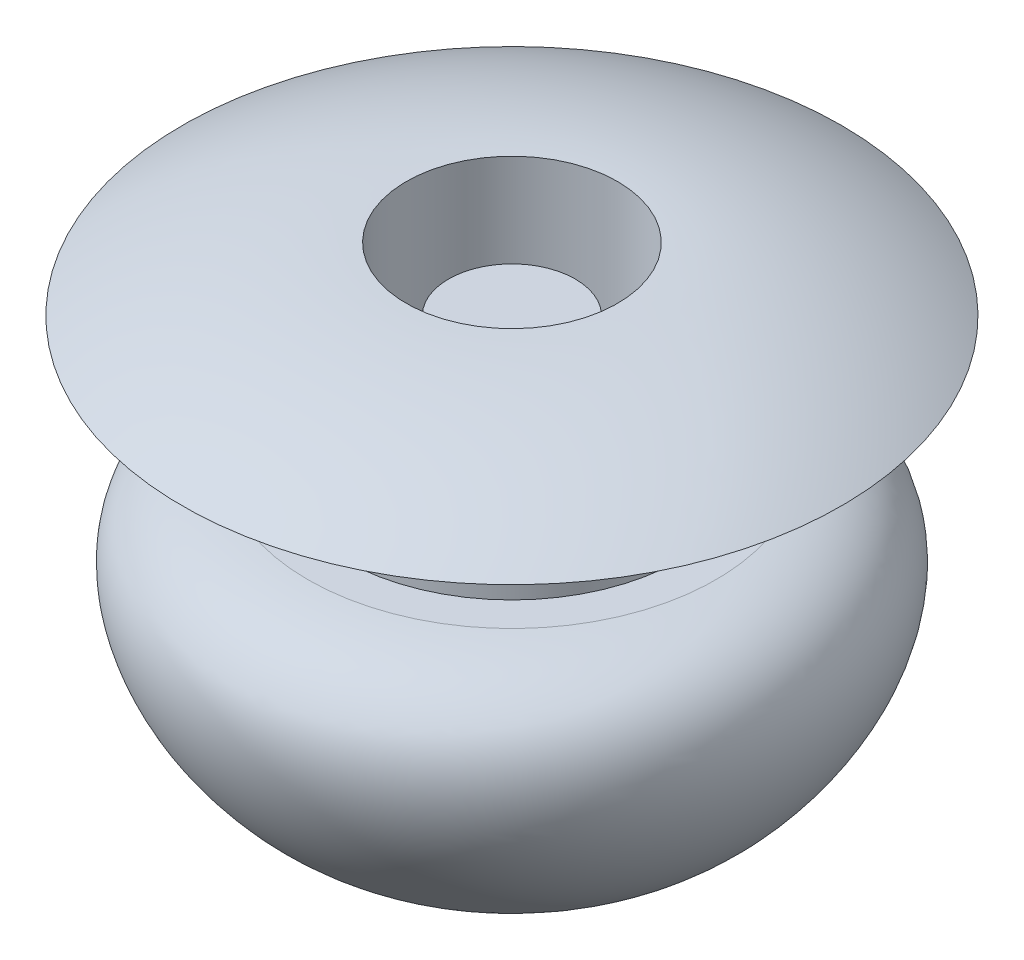
SolidWorks part; units mm, degrees
material "AISI 316 Stal nierdzewna odprężona (SS)"
ref_plane "Płaszczyzna przednia" through (0, 0, 0) normal (0, 0, 1) x (1, 0, 0)
ref_plane "Płaszczyzna górna" through (0, 0, 0) normal (0, 1, 0) x (1, 0, 0)
ref_plane "Płaszczyzna prawa" through (0, 0, 0) normal (1, 0, 0) x (0, 0, -1)
sketch "Szkic1" plane through (0, 0, 0) normal (1, 0, 0) x (0, 0, -1)
  line L1 (0, 0) -> (-0.75, 0)
  line L2 (-0.75, 0) -> (-0.75, -1.7007)
  line L3 (-0.75, -1.7007) -> (-1.25, -1.7007)
  line L4 (-1.25, -1.7007) -> (-1.25, 0.75)
  line L5 (-3.9, 0) -> (-2, 0)
  line L6 (-2, 0) -> (-2, -1.5)
  line L7 (-2, -1.5) -> (-2.4139, -1.5)
  line L8 (0, 0) -> (0, 0.4842) construction
  line L9 (0, -1.7007) -> (0, 0)
  line L10 (0, -1.7007) -> (0, -3.2007)
  line L11 (-10.4007, -1.5) -> (-6.4007, -1.5) construction
  arc A0 (-1.25, 0.75) -> (-3.9, 0) centre (-1.25, -4.3067) ccw
  ellipse E0 centre (0, -2.4507) end of major axis (-1.75, -2.4507) minor radius 0.75 (-0.956, -3.0789) -> (0, -3.2007) ccw
  spline S0 degree 3 poles (-2.4139, -1.5) (-3.8675, -1.6697) (-3.5289, -3.802) (-1.084, -5.3735) (-0.2718, -3.3749) (-0.956, -3.0789) knots 0 0 0 0 0.464993 0.721928 1 1 1 1
  point P14 (0, -7.2984)
  point P15 (0, -5.7984)
  point P25 (0, -3.447)
  point P27 (0, 0)
  point P29 (0, 0)
  point P30 (0, 0)
  point P31 (0, -2.4229)
  point P32 (0, -0.1275)
  dimension "D1" = 7.8
  dimension "D2" = 2.5
  dimension "D3" = 4
  dimension "D4" = 0.75
  dimension "D5" = 1.5
  dimension "D6" = 1.5
  dimension "D7" = 3.5
  dimension "D8" = 3.1855
  dimension "D9" = 2.5026
  dimension "D10" = 1.9
  dimension "D11" = 1.5789
  dimension "D12" = 0.5792
  dimension "D13" = 4.8278
  dimension "D14" = 3.3858
  dimension "D15" = 2.8395
  dimension "D16" = 1.25
  dimension "D17" = 0.6409
  dimension "D18" = 0.956
revolve "Obrót1" add sketch "Szkic1" angle 360 about L8
